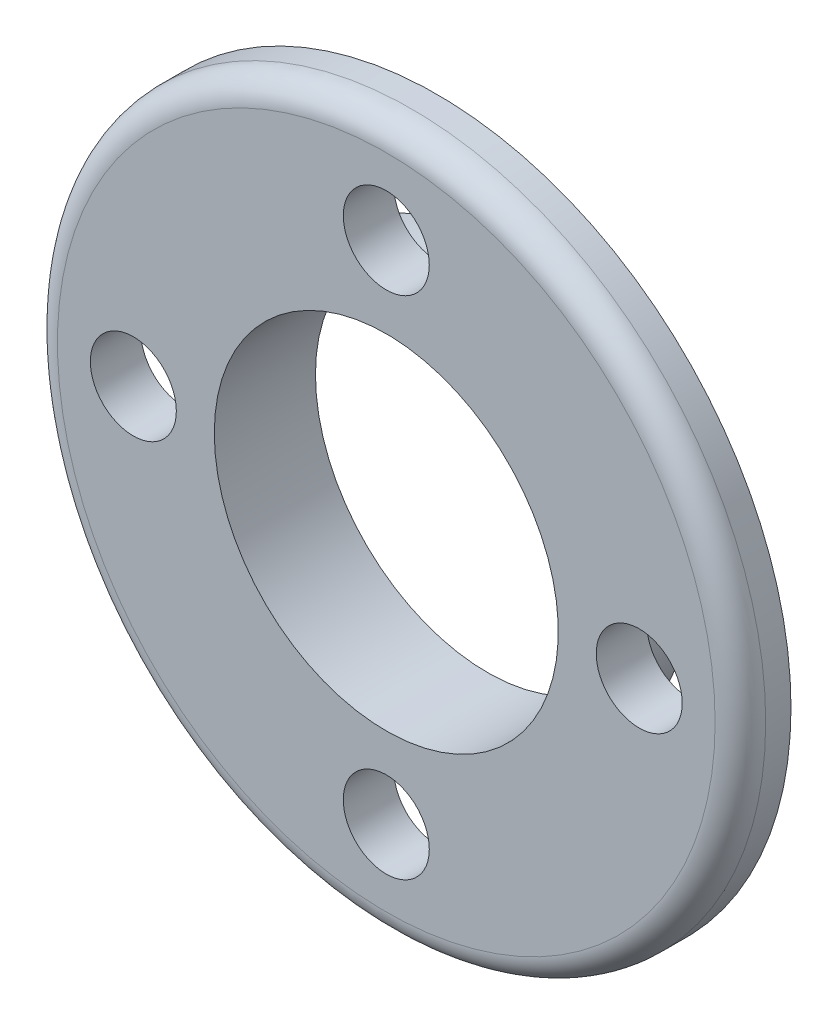
SolidWorks part; units mm, degrees
ref_plane "Front Plane" through (0, 0, 0) normal (0, 0, 1) x (1, 0, 0)
ref_plane "Top Plane" through (0, 0, 0) normal (0, 1, 0) x (1, 0, 0)
ref_plane "Right Plane" through (0, 0, 0) normal (1, 0, 0) x (0, 0, -1)
ref_axis "X-Axis" through (88.99, 0, 0) along (-1, 0, 0)
ref_axis "Y-Axis" through (0, 0, -88.99) along (0, 0, 1)
ref_axis "Z-Axis" through (0, -55, 0) along (0, 1, 0)
sketch "Sketch1" plane through (0, 0, 0) normal (1, 0, 0) x (0, 0, -1)
  line L1 (-1, 14) -> (1, 14)
  line L2 (-1, 14) -> (-1, 6.8)
  line L4 (1, 14) -> (1, 8)
  line L7 (1, 8) -> (3, 8)
  line L8 (3, 6.8) -> (3, 8)
  line L9 (-1, 6.8) -> (3, 6.8)
  line L11 (88.99, 0) -> (-88.99, 0) construction
  line L12 (0, -55) -> (0, 55) construction
  point P8 (0, 14)
  dimension "D1" = 8
  dimension "D2" = 1.2
  dimension "D3" = 6
  dimension "D4" = 2
  dimension "D5" = 2
revolve "Revolve1" add sketch "Sketch1" angle 360 about axis through (0, 0, -88.99) along (0, 0, 1)
sketch "Sketch3" plane through (0, 0, 1) normal (0, 0, 1) x (1, 0, 0)
  line L0 (88.99, 0) -> (-88.99, 0) construction
  point P0 (10, 0)
  dimension "D1" = 10
hole_wizard "M3 Clearance Hole1" positions "3DSketch1" profile "Sketch4" hole size "M3" standard "ANSI Metric"
sketch3d "3DSketch1"
  point P0 (10, 0, 1)
sketch "Sketch4" plane through (10, 0, 1) normal (1, 0, 0) x (0, -1, 0)
  line L0 (0, 0) -> (0, 9.0215)
  line L1 (0, 9.0215) -> (1.7, 8)
  line L2 (1.7, 8) -> (1.7, 0)
  line L5 (1.7, 0) -> (0, 0)
  line L10 (0, 9.0215) -> (-1.7, 8) construction
  line L11 (0, -6.35) -> (0, 107.95) construction
  dimension "Hole Dia." = 3.4
  dimension "Hole Depth" = 8
  dimension "Drill Angle" = 118
pattern_circular "CirPattern1" count 4 over 360 about axis through (0, 0, -88.99) along (0, 0, 1) of "M3 Clearance Hole1"
fillet "Fillet1" radius 1 1 edges at (-14, 0, 1)
